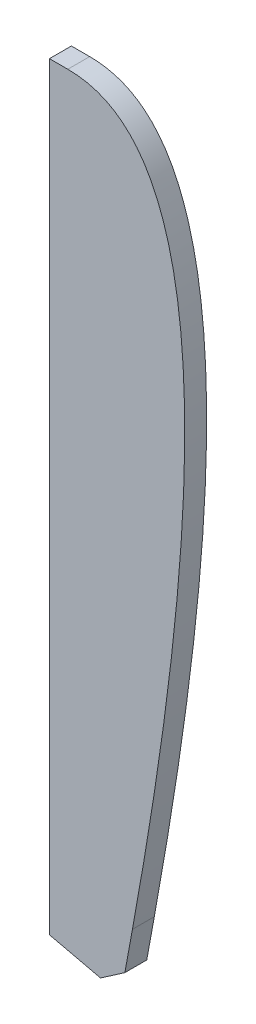
SolidWorks part; units mm, degrees
material "MDF"
ref_plane "Front Plane" through (0, 0, 0) normal (0, 0, 1) x (1, 0, 0)
ref_plane "Top Plane" through (0, 0, 0) normal (0, 1, 0) x (1, 0, 0)
ref_plane "Right Plane" through (0, 0, 0) normal (1, 0, 0) x (0, 0, -1)
sketch "Sketch2" plane through (0, 0, 0) normal (0, 0, 1) x (1, 0, 0)
  line L0 (12.7, -5480.4165) -> (54.1406, -5490.0476)
  line L1 (12.7, -5040.3314) -> (12.7, -5577.1295) construction
  line L2 (48.0775, -5488.6385) -> (326.4096, -5553.3247) construction
  line L3 (12.7, -5480.4165) -> (12.7, -5040.3314)
  line L4 (54.1406, -5490.0476) -> (136.525, -5040.3314)
  line L5 (136.525, -5040.3314) -> (12.7, -5040.3314)
  dimension "D1" = 457.2
  dimension "D2" = 42.545
  dimension "D3" = 123.825
extrude "Boss-Extrude1" add sketch "Sketch2" against normal blind 12.7
fillet "Fillet1" radius 406.4 1 edges at (136.525, -5040.3314, -6.35)
chamfer "Chamfer1" distance 12.7 angle 45 1 edges at (54.1406, -5490.0476, -6.35)
